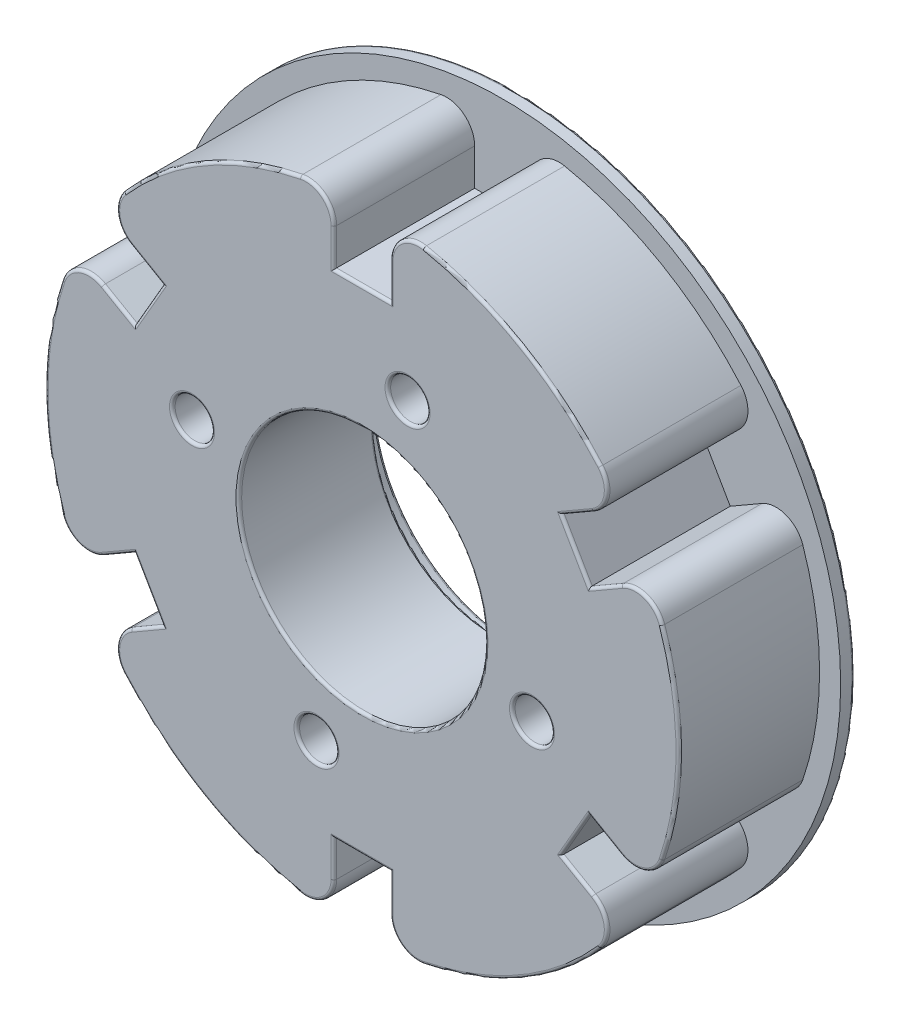
SolidWorks part; units mm, degrees
ref_plane "Front Plane" through (0, 0, 0) normal (0, 0, 1) x (1, 0, 0)
ref_plane "Top Plane" through (0, 0, 0) normal (0, 1, 0) x (1, 0, 0)
ref_plane "Right Plane" through (0, 0, 0) normal (1, 0, 0) x (0, 0, -1)
sketch "Sketch1" plane through (0, 0, 0) normal (0, 0, 1) x (1, 0, 0)
  circle A0 centre (0, 0) radius 28.575
  dimension "D1" = 57.15
extrude "Boss-Extrude1" add sketch "Sketch1" along normal mid plane 12.7
sketch "Sketch2" plane through (0, 0, -6.35) normal (0, 0, 1) x (1, 0, 0)
  circle A0 centre (0, 0) radius 30.48
  dimension "D1" = 60.96
extrude "Boss-Extrude2" add sketch "Sketch2" against normal blind 1.27
sketch "Sketch3" plane through (0, 0, -6.35) normal (0, 0, 1) x (1, 0, 0)
  line L0 (0, 28.575) -> (0, -30.48) construction
  line L1 (-2.54, 29.845) -> (-2.54, 22.225)
  line L2 (2.54, 29.845) -> (2.54, 22.225)
  line L3 (-2.54, 22.225) -> (2.54, 22.225)
  line L4 (-2.54, 29.845) -> (2.54, 29.845)
  circle A1 centre (0, 0) radius 28.575 construction
  circle A2 centre (0, 0) radius 30.48 construction
  dimension "D2" = 6.35
  dimension "D1" = 2.54
  dimension "D3" = 7.62
extrude "Cut-Extrude1" cut sketch "Sketch3" along normal through all
fillet "Fillet1" radius 2.54 2 edges at (2.54, 28.4619, 0) (-2.54, 28.4619, 0)
ref_axis "Axis2" through (0, 0, 7.0485) along (0, 0, -1)
pattern_circular "CirPattern1" count 6 over 360 about axis through (0, 0, 7.0485) along (0, 0, -1) of "Cut-Extrude1", "Fillet1"
sketch "Sketch6" plane through (0, 0, -7.62) normal (0, 0, -1) x (-1, 0, 0)
  circle A1 centre (0, 0) radius 11.1125
  dimension "D1" = 22.225
extrude "Cut-Extrude4" cut sketch "Sketch6" along normal through all and the other way through all contours A1 region at (0, 0, -7.62)
sketch "Sketch7" plane through (0, 0, -7.62) normal (0, 0, -1) x (-1, 0, 0)
  line L0 (0, 0) -> (-15.3341, -4.1088) construction
  circle A0 centre (-15.3341, -4.1088) radius 1.778
  circle A1 centre (-4.1088, 15.3341) radius 1.778
  circle A2 centre (15.3341, 4.1088) radius 1.778
  circle A3 centre (4.1088, -15.3341) radius 1.778
  point P13 (0, 0)
  dimension "D2" = 3.556
  dimension "D1" = 15.875
  dimension "D4" = 15
  dimension "D3" = 4
extrude "Cut-Extrude5" cut sketch "Sketch7" against normal through all both
sketch "Sketch9" plane through (0, 0, -7.62) normal (0, 0, -1) x (-1, 0, 0)
  circle A0 centre (0, 0) radius 12.7
  dimension "D1" = 25.4
extrude "Cut-Extrude6" cut sketch "Sketch9" against normal blind 1.778
fillet "Fillet2" radius 0.254 48 edges at (-11.1125, 0, -5.842) (30.48, 0, -7.62) (-5.8868, -15.3341, -7.62) (-17.1121, 4.1088, -7.62) (2.3308, 15.3341, -7.62) (13.5561, -4.1088, -7.62) (-12.7, 0, -7.62) (-3.4687, 27.4981, 6.35) (-2.54, 23.8798, 6.35) (0, 22.225, 6.35) (2.54, 23.8798, 6.35) (3.4687, 27.4981, 6.35) (14.2875, 24.7467, 6.35) (22.0797, 16.753, 6.35) (19.4105, 14.1396, 6.35) (19.2474, 11.1125, 6.35) (21.9505, 9.7402, 6.35) (25.5483, 10.7451, 6.35) (28.575, 0, 6.35) (25.5483, -10.7451, 6.35) (21.9505, -9.7402, 6.35) (19.2474, -11.1125, 6.35) (19.4105, -14.1396, 6.35) (22.0797, -16.753, 6.35) (14.2875, -24.7467, 6.35) (3.4687, -27.4981, 6.35) (2.54, -23.8798, 6.35) (0, -22.225, 6.35) (-2.54, -23.8798, 6.35) (-3.4687, -27.4981, 6.35) (-14.2875, -24.7467, 6.35) (-22.0797, -16.753, 6.35) (-19.4105, -14.1396, 6.35) (-19.2474, -11.1125, 6.35) (-21.9505, -9.7402, 6.35) (-25.5483, -10.7451, 6.35) (-28.575, 0, 6.35) (-25.5483, 10.7451, 6.35) (-21.9505, 9.7402, 6.35) (-19.2474, 11.1125, 6.35) (-19.4105, 14.1396, 6.35) (-22.0797, 16.753, 6.35) (-14.2875, 24.7467, 6.35) (-11.1125, 0, 6.35) (-5.8868, -15.3341, 6.35) (-17.1121, 4.1088, 6.35) (2.3308, 15.3341, 6.35) (13.5561, -4.1088, 6.35)
